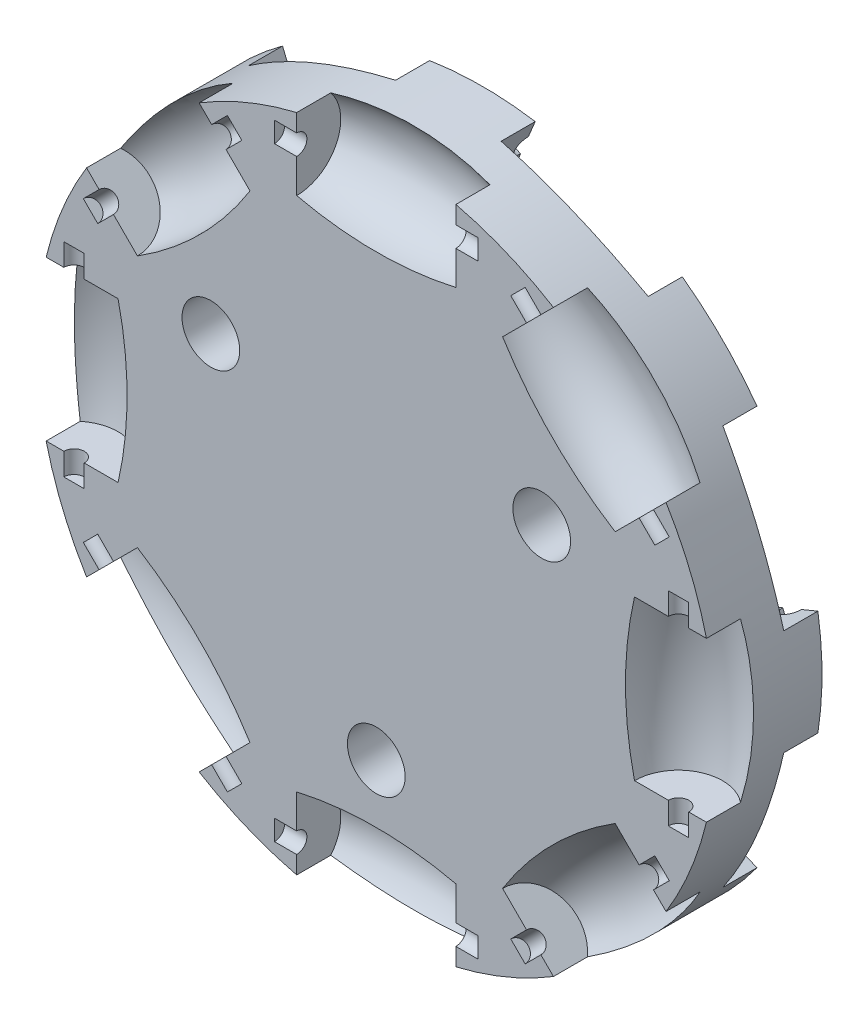
SolidWorks part; units mm, degrees
ref_plane "Front Plane" through (0, 0, 0) normal (0, 0, 1) x (1, 0, 0)
ref_plane "Top Plane" through (0, 0, 0) normal (0, 1, 0) x (1, 0, 0)
ref_plane "Right Plane" through (0, 0, 0) normal (1, 0, 0) x (0, 0, -1)
sketch "Sketch1" plane through (0, 0, 0) normal (0, 0, 1) x (1, 0, 0)
  circle A0 centre (0, 0) radius 25.4
  point P6 (-12.0183, -8.0692)
  point P7 (-18.8859, -8.736)
  point P11 (0, 0)
  point P12 (0, 0)
  dimension "D1" = 50.8
extrude "Boss-Extrude1" add sketch "Sketch1" along normal mid plane 7.9375
ref_plane "Plane1" through (0, 0, 3.9688) normal (0, 0, 1) x (1, 0, 0)
ref_plane "Plane2" through (0, 0, -3.9688) normal (0, 0, 1) x (1, 0, 0)
sketch "Sketch5" plane through (0, 0, 3.9688) normal (0, 0, 1) x (1, 0, 0)
  line L0 (-5.9531, 25.8994) -> (-5.9531, 22.606)
  line L1 (-5.9531, 22.606) -> (5.9531, 22.606)
  line L2 (5.9531, 22.606) -> (5.9531, 25.8994)
  line L3 (-5.9531, 22.606) -> (-8.0326, 22.606) construction
  arc A2 (-5.9531, 25.8994) -> (5.9531, 25.8994) centre (0, 0) cw
  point P2 (0, 26.5748)
  point P7 (0, 22.606)
  dimension "D1" = 11.9062
  dimension "D2" = 7.9375
  dimension "D3" = 22.606
revolve "Cut-Revolve5" cut sketch "Sketch5" angle 360 about L1
sketch "Sketch8" plane through (0, 0, -3.9688) normal (0, 0, 1) x (1, 0, 0)
  line L0 (4.4113, 26.2061) -> (3.151, 23.1634)
  line L1 (3.151, 23.1634) -> (14.1509, 18.6071)
  line L2 (14.1509, 18.6071) -> (15.4112, 21.6497)
  line L3 (3.151, 23.1634) -> (-2.0499, 25.3177) construction
  line L4 (0, 0) -> (9.7202, 23.4665) construction
  line L5 (0, 0) -> (0, 7.8748) construction
  arc A0 (4.4113, 26.2061) -> (15.4112, 21.6497) centre (0, 0) cw
  arc A2 (-5.9531, 24.6925) -> (5.9531, 24.6925) centre (0, 0) ccw construction
  point P2 (4.4312, 26.254)
  point P6 (8.6509, 20.8852)
  point P11 (9.7202, 23.4665)
  point P14 (10.1697, 24.5519)
  point P16 (15.5027, 21.8705)
  dimension "D1" = 11.9062
  dimension "D2" = 7.9375
  dimension "D3" = 22.5
  dimension "D4" = 22.606
revolve "Cut-Revolve6" cut sketch "Sketch8" angle 360 about L3
sketch "Sketch6" plane through (0, 0, 0) normal (1, 0, 0) x (0, 0, -1)
  arc A0 (-3.9688, 19.3126) -> (-1.4207, 24.6925) centre (-3.9688, 22.606) ccw construction
  circle A1 centre (-3.9688, 22.606) radius 0.762
  point P4 (-3.9688, 22.606)
  dimension "D1" = 1.524
extrude "Cut-Extrude2" cut sketch "Sketch6" against normal mid plane 15.24
ref_axis "Axis1" through (0, 0, -8.8615) along (0, 0, 1)
ref_plane "Plane3" through (0, 0, 0) normal (0.9239, -0.3827, 0) x (0, 0, -1)
sketch "Sketch10" plane through (0, 0, 0) normal (0.9239, -0.3827, 0) x (0, 0, -1)
  arc A1 (1.4207, 24.6925) -> (3.9688, 19.3126) centre (3.9688, 22.606) ccw construction
  circle A2 centre (3.9688, 22.606) radius 0.762
  point P4 (3.9688, 22.606)
  dimension "D1" = 1.524
extrude "Cut-Extrude3" cut sketch "Sketch10" against normal mid plane 15.24
pattern_circular "CirPattern1" count 8 over 360 about axis through (0, 0, 3.9688) along (0, 0, -1) of "Cut-Revolve5", "Cut-Revolve6", "Cut-Extrude2", "Cut-Extrude3"
sketch "Sketch16" plane through (0, 0, 3.9688) normal (0, 0, 1) x (1, 0, 0)
  circle A0 centre (0, -14.2875) radius 2.159
  circle A1 centre (-12.3733, 7.1437) radius 2.159
  circle A2 centre (12.3733, 7.1438) radius 2.159
  point P4 (-33.4047, 7.5099)
  point P5 (0, 0)
  point P9 (0, 0)
  dimension "D1" = 4.318
  dimension "D2" = 14.2875
  dimension "D3" = 3
extrude "Cut-Extrude7" cut sketch "Sketch16" against normal through all
